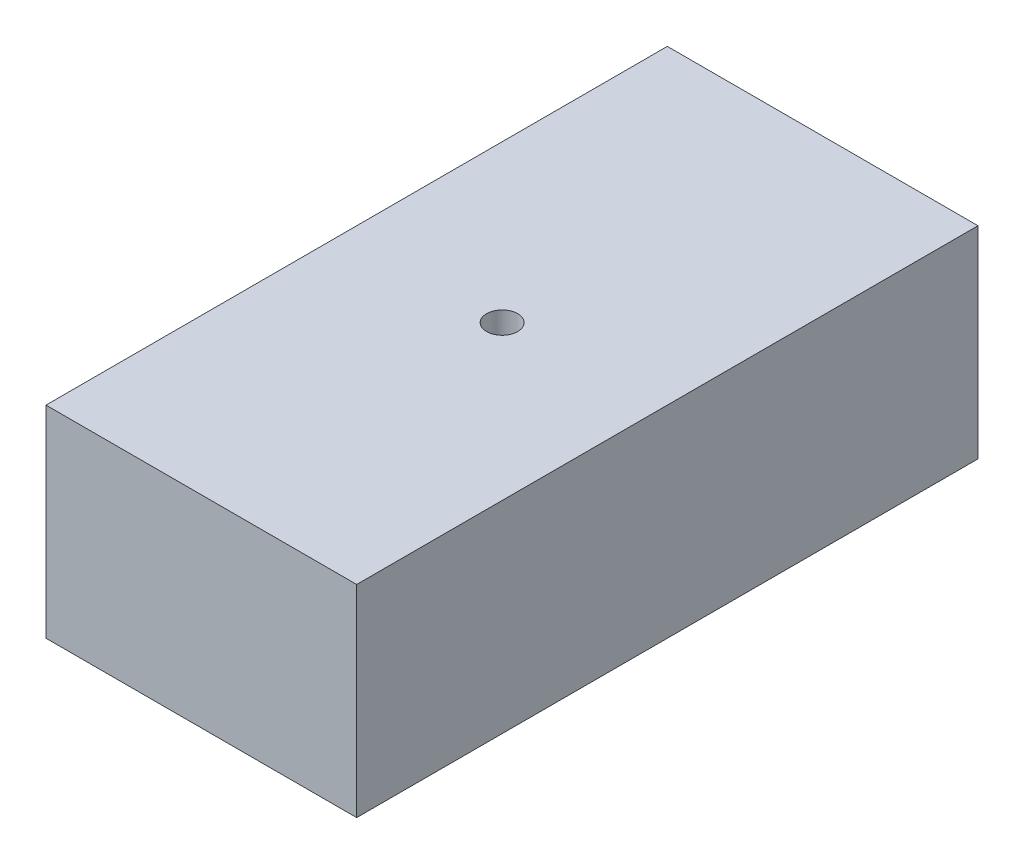
SolidWorks part; units mm, degrees
ref_plane "Front Plane" through (0, 0, 0) normal (0, 0, 1) x (1, 0, 0)
ref_plane "Top Plane" through (0, 0, 0) normal (0, 1, 0) x (1, 0, 0)
ref_plane "Right Plane" through (0, 0, 0) normal (1, 0, 0) x (0, 0, -1)
sketch "Sketch1" plane through (0, 0, 0) normal (0, 1, 0) x (1, 0, 0)
  line L1 (0, 200) -> (100, 200)
  line L2 (0, 200) -> (0, 0)
  line L3 (0, 0) -> (100, 0)
  line L4 (100, 200) -> (100, 0)
  dimension "D1" = 100
  dimension "D2" = 200
extrude "Boss-Extrude1" add sketch "Sketch1" along normal blind 65 contours L4 L1 L2 L3 region at (50, 0, -100)
hole_wizard "Ø10.0mm Dowel Hole1" positions "Sketch2" profile "Sketch4" hole size "Ø10.0" standard "ANSI Metric"
sketch "Sketch2" plane through (0, 65, 0) normal (0, 1, 0) x (1, 0, 0)
  point P0 (50.4165, 96.4034)
sketch "Sketch4" plane through (50.4165, 65, -96.4034) normal (1, 0, 0) x (0, 0, 1)
  line L0 (0, 0) -> (0, 43.0043)
  line L1 (0, 43.0043) -> (5, 40)
  line L2 (5, 40) -> (5, 0)
  line L5 (5, 0) -> (0, 0)
  line L10 (0, 43.0043) -> (-5, 40) construction
  line L11 (0, -6.35) -> (0, 107.95) construction
  dimension "Hole Dia." = 10
  dimension "Hole Depth" = 40
  dimension "Drill Angle" = 118
